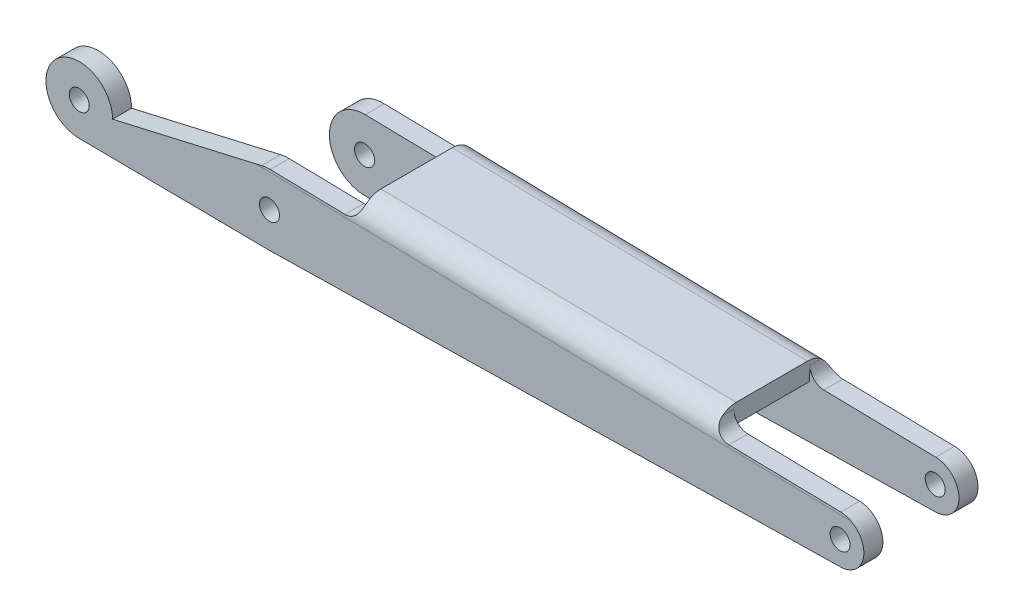
SolidWorks part; units mm, degrees
ref_plane "Front Plane" through (0, 0, 0) normal (0, 0, 1) x (1, 0, 0)
ref_plane "Top Plane" through (0, 0, 0) normal (0, 1, 0) x (1, 0, 0)
ref_plane "Right Plane" through (0, 0, 0) normal (1, 0, 0) x (0, 0, -1)
ref_plane "Plane4" through (0, 0, -7.75) normal (0, 0, 1) x (1, 0, 0)
sketch "Sketch3" plane through (0, 0, -7.75) normal (0, 0, 1) x (1, 0, 0)
  line L0 (-40, 0) -> (0, 0)
  line L1 (0, 0) -> (120, 0)
  line L2 (0.148, 7.3985) -> (120.1, 4.9995)
  line L3 (0.148, -7.3985) -> (120.1, -4.9995)
  line L4 (-0.074, -7.3996) -> (-40.07, -6.9996)
  line L5 (-33, 0) -> (-1.6594, 7.2115)
  circle A0 centre (0, 0) radius 7.4
  circle A1 centre (-40, 0) radius 7
  circle A2 centre (120, 0) radius 5.0005
extrude "Boss-Extrude1" add sketch "Sketch3" against normal blind 4 contours A2 L2 A0 L1 | A2 L1 A0 L3 | L1 A0 L0 | L0 A0 L1 | A1 L4 A0 L0 | A0 L5 L0 | A1 | A2 region at (-15.1273, 2.2057, -7.75) region at (-35.2144, -4.8337, -7.75) region at (-20.0794, -3.8144, -7.75) region at (0, 3.1407, -7.75) region at (0, -3.1407, -7.75) region at (57.6946, 3.1687, -7.75) region at (57.6946, -3.1687, -7.75) region at (123.4701, 3.4014, -7.75)
ref_plane "Plane5" through (0, 0, -27.75) normal (0, 0, -1) x (-1, 0, 0)
sketch "Sketch8" plane through (0, 0, -27.75) normal (0, 0, -1) x (-1, 0, 0)
  line L0 (-0.148, -7.3985) -> (-120.1, -4.9995)
  line L1 (-120.1, 4.9995) -> (-0.148, 7.3985)
  circle A0 centre (0, 0) radius 7.4
  circle A1 centre (-120, 0) radius 5.0005
extrude "Boss-Extrude2" add sketch "Sketch8" along normal blind 4 separate body contours A0 | A1 L0 A0 L1 | A1 region at (57.6946, 0, -27.75) region at (0, 0, -27.75) region at (120, 0, -27.75)
sketch "Sketch9" plane through (0.148, 7.3985, 0) normal (0.02, 0.9998, 0) x (0.9998, -0.02, 0)
  line L0 (119.976, 31.75) -> (0, 31.75) construction
  line L1 (18.7149, 31.75) -> (93.459, 31.75)
  line L2 (18.7149, 31.75) -> (18.7149, 7.75)
  line L3 (18.7149, 7.75) -> (93.459, 7.75)
  line L4 (93.459, 31.75) -> (93.459, 7.75)
  line L5 (0, 7.75) -> (119.976, 7.75) construction
extrude "Boss-Extrude3" add sketch "Sketch9" along normal blind 4
fillet "Fillet1" radius 4.5 2 edges at (56.3037, 10.2762, -7.75) (56.3037, 10.2762, -31.75)
fillet "Fillet2" radius 3 4 edges at (18.8592, 7.0243, -9.7639) (18.8592, 7.0243, -29.7361) (93.5882, 5.5297, -9.7639) (93.5882, 5.5297, -29.7361)
ref_axis "Axis1" through (0, 0, -54.1743) along (0, 0, 1)
ref_axis "Axis2" through (-40, 0, -22.218) along (0, 0, 1)
ref_axis "Axis3" through (120, 0, -48.8934) along (0, 0, 1)
sketch "Sketch10" plane through (0, 0, -7.75) normal (0, 0, 1) x (1, 0, 0)
  circle A0 centre (-40, 0) radius 2.1
  circle A1 centre (0, 0) radius 2.1
  circle A2 centre (120, 0) radius 2.1
extrude "Cut-Extrude1" cut sketch "Sketch10" against normal through all
